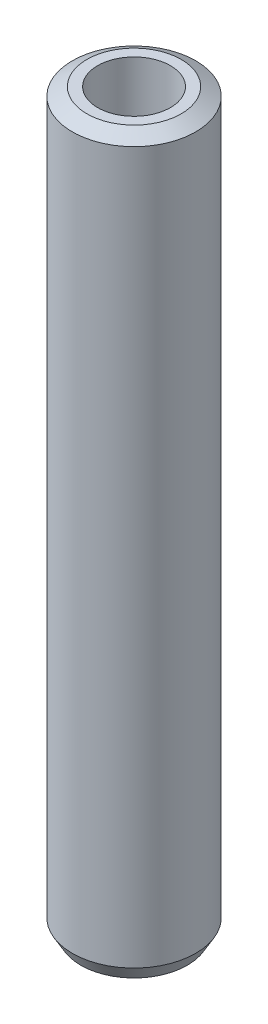
SolidWorks part; units mm, degrees
ref_plane "Front Plane" through (0, 0, 0) normal (0, 0, 1) x (1, 0, 0)
ref_plane "Top Plane" through (0, 0, 0) normal (0, 1, 0) x (1, 0, 0)
ref_plane "Right Plane" through (0, 0, 0) normal (1, 0, 0) x (0, 0, -1)
sketch "Sketch1" plane through (0, 0, 0) normal (0, 1, 0) x (1, 0, 0)
  circle A0 centre (0, 0) radius 25
  dimension "SHAFT_OD" = 50
extrude "Boss-Extrude1" add sketch "Sketch1" along normal blind 297.6045
sketch "Sketch2" plane through (0, 0, 0) normal (0, 1, 0) x (1, 0, 0)
  circle A0 centre (0, 0) radius 14.7536
  dimension "BORE_D" = 29.5072
extrude "Cut-Extrude1" cut sketch "Sketch2" along normal through all
chamfer "Chamfer1" distance 3.4004 angle 60 2 edges at (0, 297.6045, 25) (0, 0, 25) first distance on face at (0, 297.6045, 25) first distance on face at (0, 0, 14.7536)
